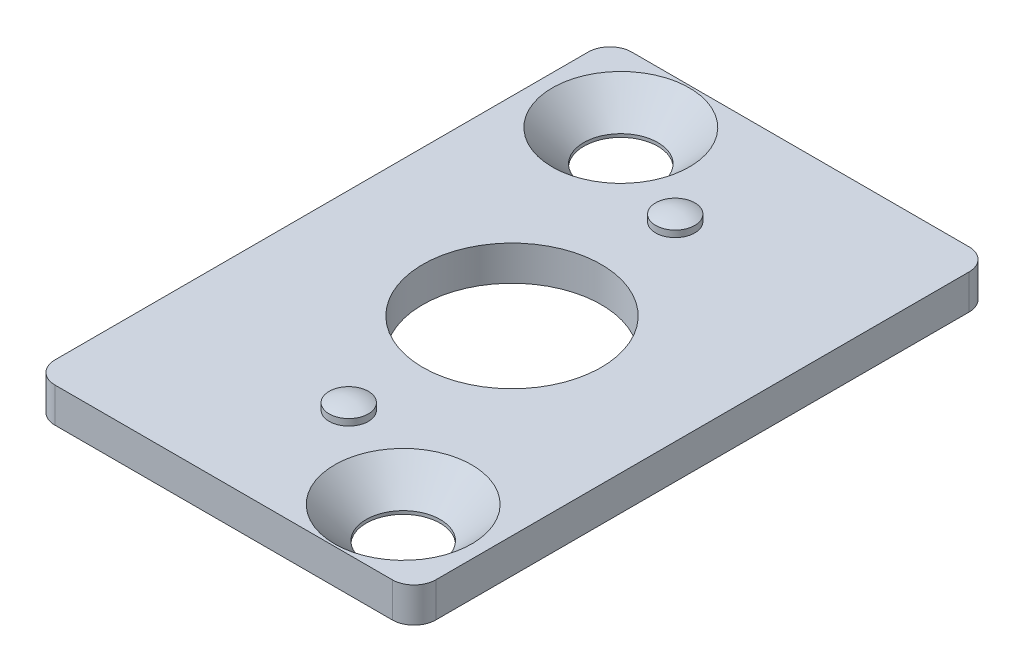
SolidWorks part; units mm, degrees
material "Chrome Stainless Steel"
ref_plane "Front Plane" through (0, 0, 0) normal (0, 0, 1) x (1, 0, 0)
ref_plane "Top Plane" through (0, 0, 0) normal (0, 1, 0) x (1, 0, 0)
ref_plane "Right Plane" through (0, 0, 0) normal (1, 0, 0) x (0, 0, -1)
sketch "BaseS" plane through (0, 0, 0) normal (0, 1, 0) x (1, 0, 0)
  line L1 (-8.75, 13.25) -> (8.75, 13.25)
  line L2 (-8.75, 13.25) -> (-8.75, -13.25)
  line L3 (-8.75, -13.25) -> (8.75, -13.25)
  line L4 (8.75, 13.25) -> (8.75, -13.25)
  line L5 (-8.75, 13.25) -> (8.75, -13.25) construction
  line L6 (-8.75, -13.25) -> (8.75, 13.25) construction
  point P0 (0, 0)
  dimension "Width" = 17.5
  dimension "Length" = 26.5
extrude "BASE" add sketch "BaseS" against normal blind 1.6
hole_wizard "CSK for M3 Flat Head Machine Screw1" positions "Sketch2" profile "Sketch3" countersink size "M3" standard "ANSI Metric"
sketch "Sketch2" plane through (0, 0, 0) normal (0, 1, 0) x (1, 0, 0)
  line L0 (-8.75, 13.25) -> (-8.75, -13.25) construction
  line L1 (8.75, -13.25) -> (8.75, 13.25) construction
  line L2 (8.75, 13.25) -> (-8.75, 13.25) construction
  line L3 (-8.75, -13.25) -> (8.75, -13.25) construction
  point P0 (-5, 10)
  point P2 (5, -10)
  dimension "XLoc1" = 3.75
  dimension "XLoc2" = 3.75
  dimension "YLoc1" = 3.25
  dimension "YLoc2" = 3.25
  dimension "YH2HRefDim" = 20
  dimension "XH2HRefDim" = 10
sketch "Sketch3" plane through (-5, 0, -10) normal (1, 0, 0) x (0, 0, 1)
  line L0 (0, 0) -> (0, 12.0215)
  line L1 (0, 12.0215) -> (1.7, 11)
  line L2 (1.7, 11) -> (1.7, 1.45)
  line L3 (1.7, 1.45) -> (3.15, 0)
  line L5 (3.15, 0) -> (0, 0)
  line L6 (-1.7, 1.45) -> (-3.15, 0) construction
  line L10 (0, 12.0215) -> (-1.7, 11) construction
  line L11 (0, -6.35) -> (0, 107.95) construction
  dimension "Hole Dia." = 3.4
  dimension "Hole Depth" = 11
  dimension "Near C'Sink Dia." = 6.3
  dimension "Near C'Sink Angle" = 90
  dimension "Drill Angle" = 118
sketch "BoreS" plane through (0, 0, 0) normal (0, 1, 0) x (1, 0, 0)
  circle A0 centre (0, 0) radius 4.1
  dimension "Dia" = 8.2
extrude "BORE" cut sketch "BoreS" against normal through all
sketch "LockingFeatureS" plane through (0, 0, 0) normal (0, 1, 0) x (1, 0, 0)
  line L0 (0, 0) -> (0, 7.5) construction
  circle A0 centre (0, 7.5) radius 0.9
  circle A1 centre (0, 0) radius 4.1 construction
  dimension "Dia" = 1.8
  dimension "XLoc" = 7.5
extrude "LOCKING FEATURE" add sketch "LockingFeatureS" along normal blind 0.3
dome "LF DOME" faces to dome 1 distance 0.2 reverse direction no elliptical dome no face at (0, 0.3, -6.6) parameters "Height"=0.2
mirror "LF HM" about plane through (0, 0, 0) normal (0, 0, 1) of "LOCKING FEATURE", "LF DOME"
sketch "LFBottomCut" plane through (0, -1.6, 0) normal (0, -1, 0) x (-1, 0, 0)
  circle A0 centre (0, 7.5) radius 0.9
  circle A1 centre (0, -7.5) radius 0.9
  circle A2 centre (0, 7.5) radius 0.9 construction
extrude "LF BOTTOM CUT" cut sketch "LFBottomCut" against normal blind 0.3
fillet "BASE FILLET" radius 1 4 edges at (-8.75, -0.8, -13.25) (8.75, -0.8, -13.25) (8.75, -0.8, 13.25) (-8.75, -0.8, 13.25)
